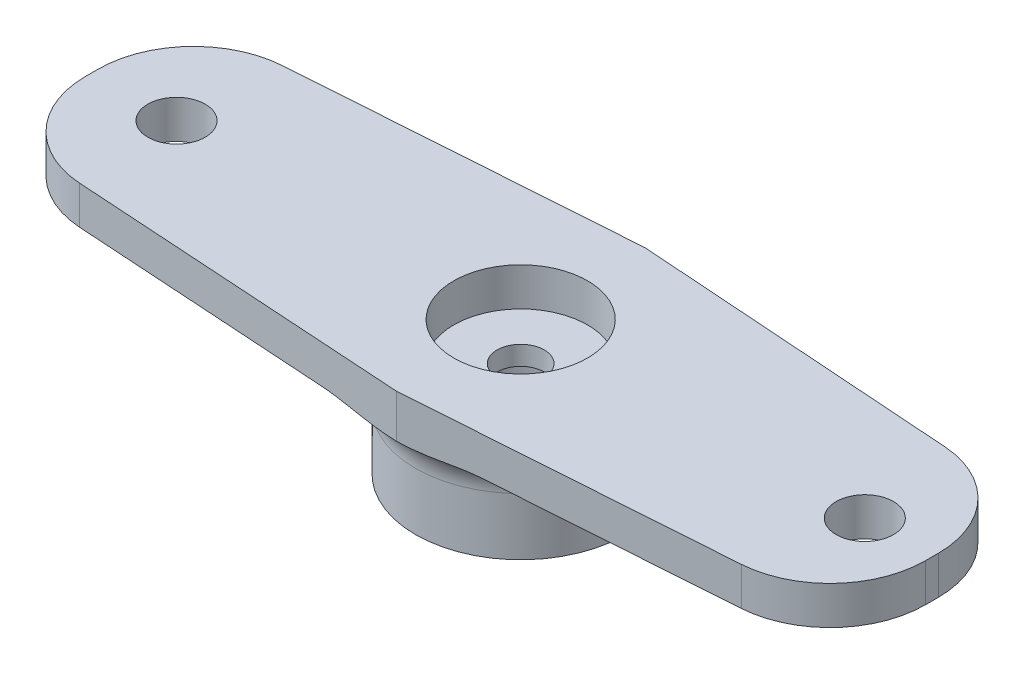
SolidWorks part; units mm, degrees
ref_plane "Front Plane" through (0, 0, 0) normal (0, 0, 1) x (1, 0, 0)
ref_plane "Top Plane" through (0, 0, 0) normal (0, 1, 0) x (1, 0, 0)
ref_plane "Right Plane" through (0, 0, 0) normal (1, 0, 0) x (0, 0, -1)
sketch "Sketch1" plane through (0, 0, 0) normal (0, 1, 0) x (1, 0, 0)
  line L0 (0, 6.5) -> (-22.385, 4.9393)
  line L1 (18, 0) -> (-18, 0) construction
  line L2 (-22.385, 4.9393) -> (-22.385, -5.0607)
  line L4 (21.514, 5) -> (21.514, -5)
  line L6 (0, -6.5) -> (-22.385, -5.0607)
  line L7 (0, 6.5) -> (21.514, 5)
  line L8 (0, -6.5) -> (21.514, -5)
  circle A0 centre (0, 0) radius 3.5
  circle A1 centre (-18, 0) radius 1.5
  circle A2 centre (18, 0) radius 1.5
  point P3 (21.514, 0)
  dimension "D1" = 7
  dimension "D2" = 3
  dimension "D3" = 3
  dimension "D4" = 13
  dimension "D5" = 6.5
  dimension "D6" = 10
  dimension "D7" = 10
  dimension "D8" = 0
  dimension "D9" = 18
  dimension "D10" = 18
extrude "Boss-Extrude1" add sketch "Sketch1" along normal blind 2
fillet "Fillet2" radius 5 4 edges at (-22.385, 1, 5.0607) (-22.385, 1, -4.9393) (21.514, 1, -5) (21.514, 1, 5)
sketch "Sketch2" plane through (0, 0, 0) normal (0, 1, 0) x (1, 0, 0)
  circle A0 centre (0, 0) radius 5.5
  circle A1 centre (0, 0) radius 1.2355
  dimension "D1" = 11
extrude "Boss-Extrude2" add sketch "Sketch2" against normal blind 5
fillet "Fillet3" radius 2 1 edges at (0, 0, 5.5)
sketch "Sketch3" plane through (0, 0, 0) normal (0, 1, 0) x (1, 0, 0)
  circle A0 centre (0, 0) radius 3
extrude "Cut-Extrude1" cut sketch "Sketch3" along normal blind 4 from surface starting at face at (0, -5, 1.2355)
